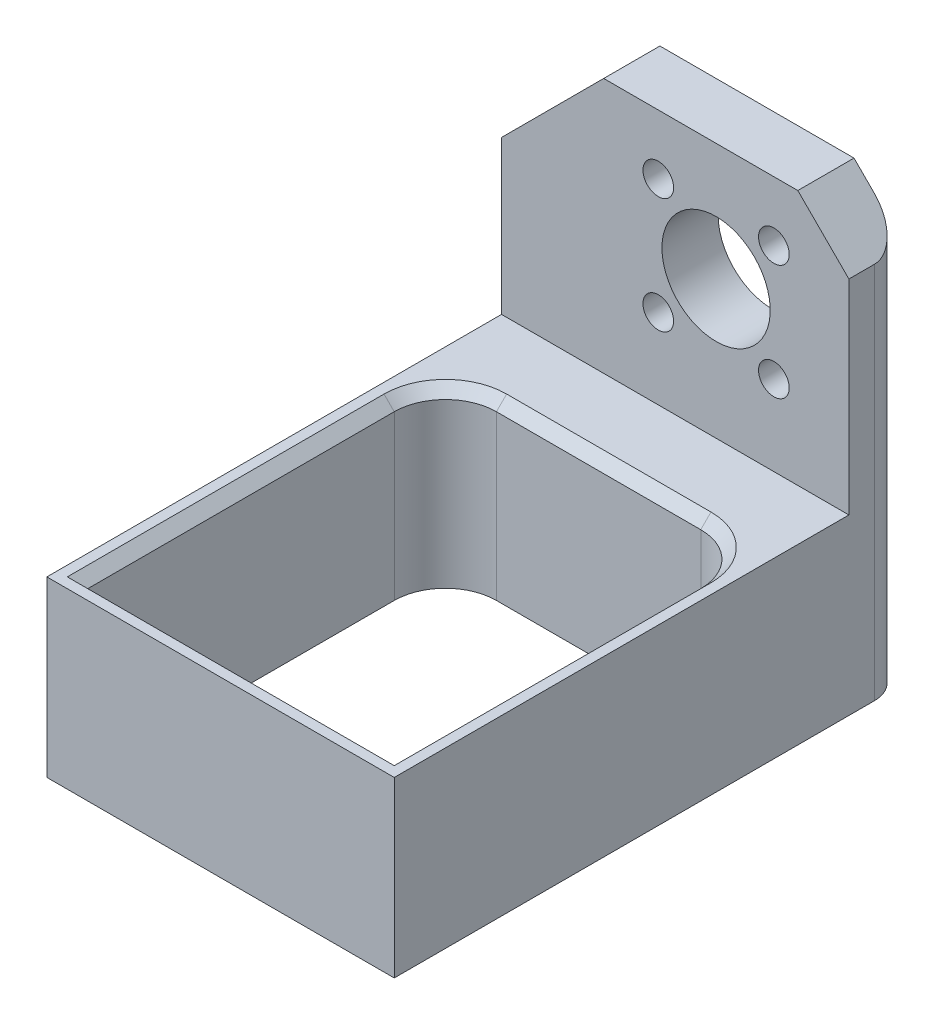
SolidWorks part; units mm, degrees
ref_plane "Płaszczyzna przednia" through (0, 0, 0) normal (0, 0, 1) x (1, 0, 0)
ref_plane "Płaszczyzna górna" through (0, 0, 0) normal (0, 1, 0) x (1, 0, 0)
ref_plane "Płaszczyzna prawa" through (0, 0, 0) normal (1, 0, 0) x (0, 0, -1)
sketch "Szkic1" plane through (0, 0, 0) normal (0, 1, 0) x (1, 0, 0)
  line L1 (-17, 25) -> (17, 25)
  line L2 (-17, 25) -> (-17, -25)
  line L3 (-17, -25) -> (17, -25)
  line L4 (17, 25) -> (17, -25)
  line L5 (-17, 25) -> (17, -25) construction
  line L6 (-17, -25) -> (17, 25) construction
  point P0 (0, 0)
  dimension "D1" = 34
  dimension "D2" = 50
extrude "Dodanie-wyciągnięcie1" add sketch "Szkic1" along normal blind 17
sketch "Szkic2" plane through (0, 17, 0) normal (0, 1, 0) x (1, 0, 0)
  line L0 (0, 25) -> (0, -25) construction
  line L1 (17, 25) -> (-17, 25) construction
  line L2 (-17, -25) -> (17, -25) construction
  line L3 (-17, 25) -> (-17, -25) construction
  line L4 (15, 7) -> (-15, 7)
  line L5 (15, 7) -> (15, -23)
  line L6 (15, -23) -> (-15, -23)
  line L7 (-15, 7) -> (-15, -23)
  line L8 (15, 7) -> (-15, -23) construction
  line L9 (15, -23) -> (-15, 7) construction
  point P6 (0, -8)
  dimension "D1" = 2
  dimension "D2" = 2
  dimension "D3" = 30
extrude "Wytnij-wyciągnięcie1" cut sketch "Szkic2" against normal blind 20
sketch "Szkic3" plane through (0, 17, 0) normal (0, 1, 0) x (1, 0, 0)
  line L0 (17, -25) -> (17, 25) construction
  line L1 (17, 25) -> (-17, 25)
  line L2 (17, 25) -> (17, 19.5)
  line L3 (17, 19.5) -> (-17, 19.5)
  line L4 (-17, 25) -> (-17, 19.5)
  line L5 (17, 25) -> (-17, 25) construction
  line L6 (-17, 25) -> (-17, -25) construction
  line L7 (-17, -25) -> (17, -25) construction
  dimension "D1" = 44.5
extrude "Dodanie-wyciągnięcie2" add sketch "Szkic3" along normal blind 25
sketch "Szkic4" plane through (0, 0, -25) normal (0, 0, -1) x (-1, 0, 0)
  line L1 (-4, 30.5) -> (-9.6569, 36.1569) construction
  line L2 (-4, 30.5) -> (-4, 38.5) construction
  line L3 (-17, 42) -> (17, 42) construction
  line L4 (0, 0) -> (0, 62.7345) construction
  line L6 (-17, 0) -> (17, 0) construction
  circle A0 centre (1.6569, 36.1569) radius 1.5
  circle A1 centre (-4, 30.5) radius 5.3
  circle A2 centre (-4, 30.5) radius 8
  circle A3 centre (-9.6569, 36.1569) radius 1.5
  circle A4 centre (-4, 30.5) radius 8
  circle A5 centre (1.6569, 24.8431) radius 1.5
  circle A6 centre (-4, 30.5) radius 8
  circle A7 centre (-9.6569, 24.8431) radius 1.5
  circle A8 centre (-4, 30.5) radius 8
  point P21 (-4, 30.5)
  dimension "D1" = 4
  dimension "D2" = 11.5
  dimension "D3" = 10.6
  dimension "D4" = 16
  dimension "D5" = 3
  dimension "D6" = 45
  dimension "D7" = 4
extrude "Wytnij-wyciągnięcie2" cut sketch "Szkic4" against normal blind 25 contours A2 A3 | A2 A3 | A2 A0 | A0 A2 | A6 A7 | A6 A7 | A4 A5 | A4 A5 | A1 region at (-2.0886, 36.5886, -25) region at (-1.1893, 35.6893, -25) region at (9.1893, 35.6893, -25) region at (10.0886, 36.5886, -25) region at (-2.0886, 24.4114, -25) region at (-1.1893, 25.3107, -25) region at (9.1893, 25.3107, -25) region at (10.0886, 24.4114, -25) region at (4, 30.5, -25)
chamfer "Sfazowanie1" distance 10 angle 45 1 edges at (-17, 42, -22.25)
chamfer "Sfazowanie2" distance 5 angle 45 1 edges at (17, 42, -22.25)
fillet "Zaokrąglenie1" radius 3 2 edges at (17, 18.5, -25) (-17, 16, -25)
sketch "Szkic5" plane through (0, 0, -7) normal (0, 0, 1) x (1, 0, 0)
  line L0 (15, 17) -> (-15, 17) construction
  line L1 (-15, 17) -> (15, 17)
  line L2 (-15, 17) -> (-15, 0)
  line L3 (-15, 0) -> (15, 0)
  line L4 (15, 17) -> (15, 0)
extrude "Wytnij-wyciągnięcie3" cut sketch "Szkic5" against normal blind 5
fillet "Zaokrąglenie2" radius 5 2 edges at (15, 8.5, -12) (-15, 8.5, -12)
chamfer "Sfazowanie3" distance 1 angle 45 6 edges at (13.5355, 17, -10.5355) (-13.5355, 17, -10.5355) (15, 17, 8) (0, 17, 23) (-15, 17, 8) (0, 17, -12)
